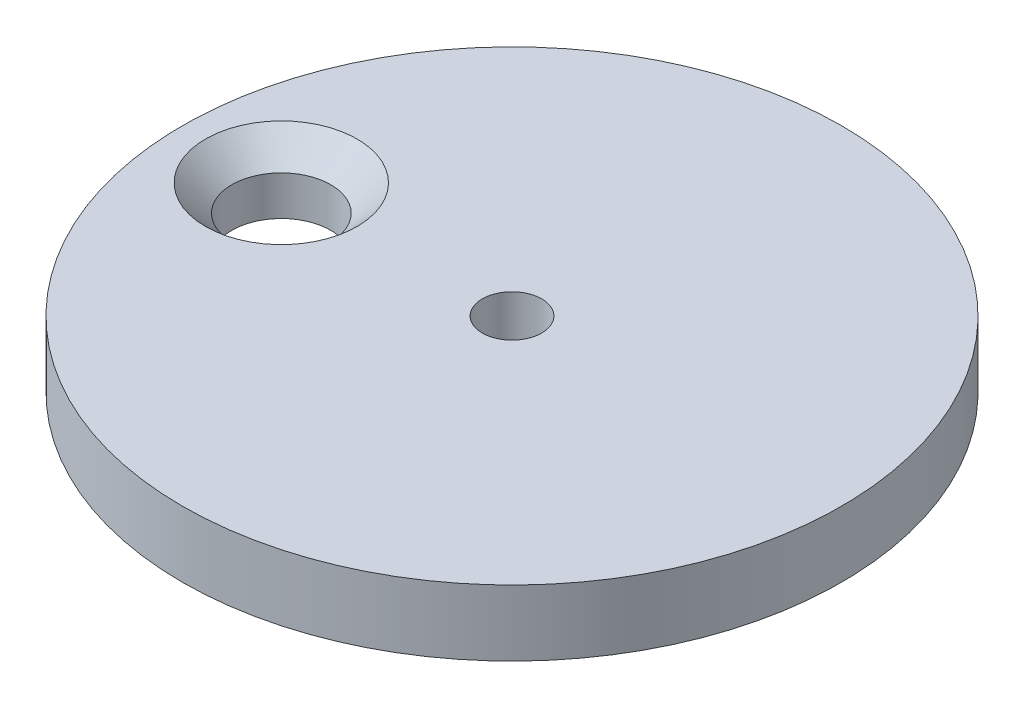
SolidWorks part; units mm, degrees
ref_plane "Front" through (0, 0, 0) normal (0, 0, 1) x (1, 0, 0)
ref_plane "Top" through (0, 0, 0) normal (0, 1, 0) x (1, 0, 0)
ref_plane "Right" through (0, 0, 0) normal (1, 0, 0) x (0, 0, -1)
sketch "Sketch1" plane through (0, 0, 0) normal (0, 1, 0) x (1, 0, 0)
  circle A0 centre (0, 0) radius 50
  circle A1 centre (-35, 0) radius 7.5
  dimension "D1" = 100
  dimension "D2" = 15
  dimension "D3" = 35
extrude "Boss-Extrude1" add sketch "Sketch1" along normal blind 10
sketch "Sketch6" plane through (0, 0, 0) normal (0, 0, 1) x (1, 0, 0)
  line L0 (0, 0) -> (0, 50) construction
  dimension "D1" = 50
chamfer "Chamfer1" distance 4 angle 45 1 edges at (-35, 10, 7.5)
sketch "Sketch2" plane through (0, 0, 0) normal (0, -1, 0) x (1, 0, 0)
  line L0 (-17, -2.5) -> (-4.43, -4.43)
  line L1 (0, 0) -> (-17, 0) construction
  line L2 (-17, 2.5) -> (-4.43, 4.43)
  line L3 (0, 0) -> (0, 50) construction
  line L4 (-2.5, 17) -> (-4.43, 4.43)
  line L5 (2.5, 17) -> (4.43, 4.43)
  line L6 (17, 2.5) -> (4.43, 4.43)
  line L7 (17, -2.5) -> (4.43, -4.43)
  line L8 (2.5, -17) -> (4.43, -4.43)
  line L9 (-2.5, -17) -> (-4.43, -4.43)
  arc A0 (-17, 2.5) -> (-17, -2.5) centre (-17, 0) ccw
  circle A1 centre (0, 0) radius 50 construction
  arc A2 (2.5, 17) -> (-2.5, 17) centre (0, 17) ccw
  arc A3 (17, -2.5) -> (17, 2.5) centre (17, 0) ccw
  arc A4 (-2.5, -17) -> (2.5, -17) centre (0, -17) ccw
  point P28 (0, 0)
  dimension "D2" = 5
  dimension "D1" = 17
  dimension "D3" = 4.43
  dimension "D4" = 4
extrude "Cut-Extrude1" cut sketch "Sketch2" against normal blind 2
sketch "Sketch3" plane through (0, 2, 0) normal (0, -1, 0) x (1, 0, 0)
  circle A0 centre (0, 0) radius 4.5
  dimension "D1" = 9
extrude "Cut-Extrude2" cut sketch "Sketch3" against normal up to next
sketch "Sketch4" plane through (0, 2, 0) normal (0, -1, 0) x (1, 0, 0)
  circle A0 centre (-16, 0) radius 1
  circle A1 centre (0, 16) radius 1
  circle A2 centre (16, 0) radius 1
  circle A3 centre (0, -16) radius 1
  point P13 (0, 0)
  dimension "D2" = 2
  dimension "D1" = 16
  dimension "D3" = 4
extrude "Cut-Extrude3" cut sketch "Sketch4" against normal offset from surface (7 mm away) 1 up to face at (0, 10, 4.5)
